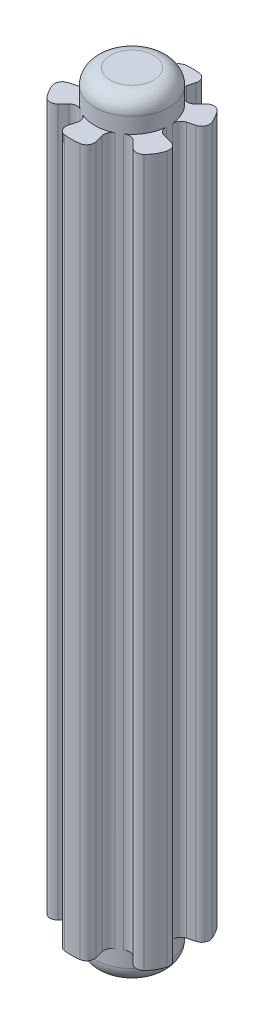
SolidWorks part; units mm, degrees
ref_plane "Front Plane" through (0, 0, 0) normal (0, 0, 1) x (1, 0, 0)
ref_plane "Top Plane" through (0, 0, 0) normal (0, 1, 0) x (1, 0, 0)
ref_plane "Right Plane" through (0, 0, 0) normal (1, 0, 0) x (0, 0, -1)
sketch "Sketch2" plane through (0, 0, 0) normal (0, 1, 0) x (1, 0, 0)
  line L0 (0, 0) -> (0.0739, 0)
  line L2 (2.3008, -0.5891) -> (3.7752, -0.9786)
  line L3 (0.0739, 0) -> (0.1042, -0.0303)
  line L4 (0, 0) -> (0.0858, -0.0446)
  line L5 (1.6802, 1.6786) -> (2.7413, 2.7388)
  line L6 (-1.6794, 1.6794) -> (-2.74, 2.74)
  line L8 (0.6147, 2.2941) -> (1.0029, 3.743)
  line L9 (-0.6147, 2.2941) -> (-1.0029, 3.743)
  line L10 (2.2941, 0.6147) -> (3.743, 1.0029)
  line L11 (0, 0) -> (0.1042, -0.0303)
  line L12 (-2.2941, 0.6147) -> (-3.743, 1.0029)
  line L13 (0.0739, 0) -> (0.0858, -0.0446)
  line L14 (-0.6147, -2.2941) -> (-1.0029, -3.743)
  line L15 (-2.2941, -0.6147) -> (-3.743, -1.0029)
  line L16 (-1.6794, -1.6794) -> (-2.74, -2.74)
  line L17 (0.6814, -2.2752) -> (1.0684, -3.7248)
  line L18 (1.7145, -1.6435) -> (2.7672, -2.6981)
  arc A0 (-2.2941, 0.6147) -> (-2.2941, -0.6147) centre (0, 0) ccw
  arc A1 (-2.74, 2.74) -> (-3.743, 1.0029) centre (0, 0) ccw
  arc A2 (1.0029, 3.743) -> (-1.0029, 3.743) centre (0, 0) ccw
  arc A3 (3.743, 1.0029) -> (2.7413, 2.7388) centre (0, 0) ccw
  arc A5 (-1.0029, -3.743) -> (1.0684, -3.7248) centre (0, 0) ccw
  arc A6 (-3.743, -1.0029) -> (-2.74, -2.74) centre (0, 0) ccw
  arc A7 (-2.74, 2.74) -> (-3.743, 1.0029) centre (0, 0) ccw
  arc A8 (1.0029, 3.743) -> (-1.0029, 3.743) centre (0, 0) ccw
  arc A9 (3.743, 1.0029) -> (2.7413, 2.7388) centre (0, 0) ccw
  arc A10 (-3.743, -1.0029) -> (-2.74, -2.74) centre (0, 0) ccw
  arc A11 (-1.0029, -3.743) -> (1.0684, -3.7248) centre (0, 0) ccw
  arc A12 (2.7672, -2.6981) -> (3.7752, -0.9786) centre (1.7753, -0.9614) ccw
  arc A13 (-0.6147, 2.2941) -> (-1.6794, 1.6794) centre (0, 0) ccw
  arc A14 (1.6802, 1.6786) -> (0.6147, 2.2941) centre (0, 0) ccw
  arc A15 (2.3008, -0.5891) -> (2.2941, 0.6147) centre (0, 0) ccw
  arc A16 (0.6814, -2.2752) -> (1.7145, -1.6435) centre (0, 0) ccw
  arc A17 (-1.6794, -1.6794) -> (-0.6147, -2.2941) centre (0, 0) ccw
  dimension "D1" = 3.875
  dimension "D2" = 2.375
extrude "Boss-Extrude1" add sketch "Sketch2" along normal blind 45 contours L16 A17 L14 A5 L17 A16 L18 A12 L2 A15 L10 A3 L5 A14 L8 A2 L9 A13 L6 A1 L12 A0 L15 A6 L11 L13 L4 L0 L3 region at (0.0225, 0, 0.0171)
sketch "Sketch4" plane through (0, 45, 0) normal (0, 1, 0) x (1, 0, 0)
  circle A0 centre (0, 0) radius 2.375
  dimension "D1" = 4.75
extrude "Boss-Extrude3" add sketch "Sketch4" along normal blind 2
fillet "Fillet1" radius 0.5 24 edges at (-2.74, 22.5, -2.74) (-1.6794, 22.5, -1.6794) (-0.6147, 22.5, -2.2941) (-1.0029, 22.5, -3.743) (1.0029, 22.5, -3.743) (0.6147, 22.5, -2.2941) (1.6802, 22.5, -1.6786) (2.7413, 22.5, -2.7388) (3.743, 22.5, -1.0029) (2.2941, 22.5, -0.6147) (2.3008, 22.5, 0.5891) (3.7752, 22.5, 0.9786) (2.7672, 22.5, 2.6981) (1.7145, 22.5, 1.6435) (0.6814, 22.5, 2.2752) (-1.6794, 22.5, 1.6794) (-2.2941, 22.5, 0.6147) (-2.2941, 22.5, -0.6147) (-0.6147, 22.5, 2.2941) (-3.743, 22.5, -1.0029) (-3.743, 22.5, 1.0029) (-2.74, 22.5, 2.74) (-1.0029, 22.5, 3.743) (1.0684, 22.5, 3.7248)
sketch "Sketch6" plane through (0, 0, 0) normal (0, -1, 0) x (1, 0, 0)
  circle A0 centre (0, 0) radius 2.375
  dimension "D1" = 4.75
extrude "Boss-Extrude5" add sketch "Sketch6" along normal blind 2
fillet "Fillet2" radius 1 2 edges at (0, 47, 2.375) (0, -2, -2.375)
